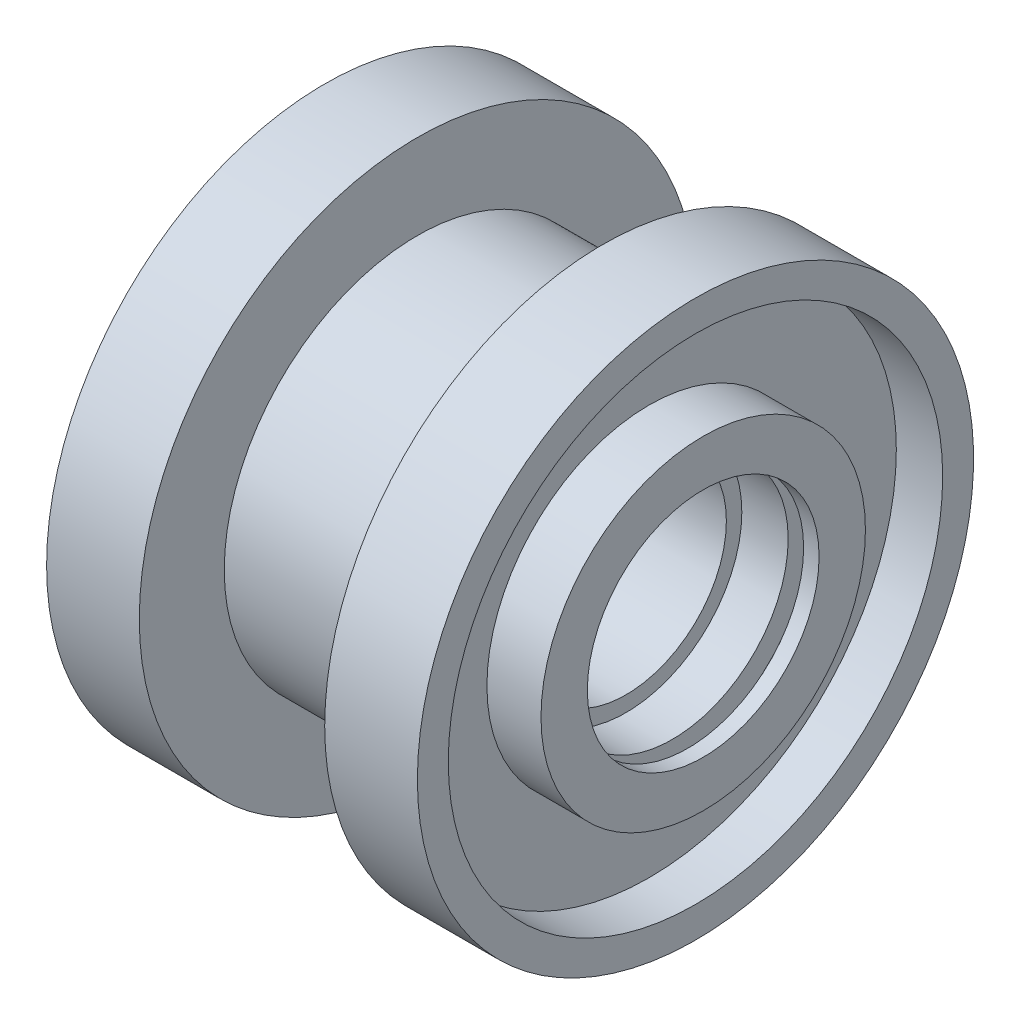
SolidWorks part; units mm, degrees
material "PS HI"
ref_plane "Płaszczyzna przednia" through (0, 0, 0) normal (0, 0, 1) x (1, 0, 0)
ref_plane "Płaszczyzna górna" through (0, 0, 0) normal (0, 1, 0) x (1, 0, 0)
ref_plane "Płaszczyzna prawa" through (0, 0, 0) normal (1, 0, 0) x (0, 0, -1)
sketch "Szkic1" plane through (0, 0, 0) normal (0, 0, 1) x (1, 0, 0)
  line L0 (-12.5, 0) -> (12.5, 0) construction
  line L1 (0, -18) -> (0, 18) construction
  line L2 (-6, 12.5) -> (6, 12.5)
  line L3 (6, 12.5) -> (6, 18)
  line L4 (6, 18) -> (12, 18)
  line L5 (12, 18) -> (12, 16)
  line L6 (12, 16) -> (9, 16)
  line L7 (9, 16) -> (9, 10.5)
  line L10 (-12, 16) -> (-9, 16)
  line L11 (-12, 18) -> (-12, 16)
  line L12 (-6, 18) -> (-12, 18)
  line L13 (-6, 12.5) -> (-6, 18)
  line L15 (12.5, 7.5) -> (12.5, 10.5)
  line L16 (12.5, 10.5) -> (9, 10.5)
  line L18 (-9, 16) -> (-9, 10.5)
  line L20 (-12.5, 7.5) -> (-12.5, 10.5)
  line L21 (-12.5, 10.5) -> (-9, 10.5)
  line L22 (12.5, 7.5) -> (11.5, 7.5)
  line L23 (7.5, 7.5) -> (7.5, 6.5)
  line L24 (7.5, 6.5) -> (-7.5, 6.5)
  line L25 (-7.5, 7.5) -> (-10.5, 7.5)
  line L26 (-7.5, 7.5) -> (-7.5, 6.5)
  line L27 (11.5, 7.5) -> (11.5, 8.9)
  line L28 (11.5, 8.9) -> (10.5, 8.9)
  line L29 (10.5, 8.9) -> (10.5, 7.5)
  line L30 (10.5, 7.5) -> (7.5, 7.5)
  line L31 (-11.5, 7.5) -> (-11.5, 8.9)
  line L32 (-10.5, 8.9) -> (-10.5, 7.5)
  line L33 (-11.5, 8.9) -> (-10.5, 8.9)
  line L34 (-11.5, 7.5) -> (-12.5, 7.5)
  point P1 (12, 17)
  point P7 (0, 0)
  point P14 (0, 7.5)
  point P15 (7.5, 7.5)
  point P21 (0, 12.5)
  point P23 (12.5, 9)
  point P32 (0, 6.5)
  point P40 (0, 0)
  point P41 (0, 0)
  point P42 (0, 0)
  point P43 (0, 0)
  dimension "D2" = 25
  dimension "D3" = 32
  dimension "D4" = 36
  dimension "D5" = 3
  dimension "D6" = 6
  dimension "D7" = 12
  dimension "D8" = 21
  dimension "D9" = 3.5
  dimension "D10" = 25
  dimension "D11" = 5
  dimension "D12" = 13
  dimension "D14" = 1
  dimension "D15" = 3
  dimension "D16" = 15
  dimension "D17" = 17.8
revolve "Obrót1" add sketch "Szkic1" angle 360 about L0
sketch "Szkic2" plane through (-12, 0, 0) normal (-1, 0, 0) x (0, 0, 1)
  line L0 (0, 18) -> (0, 16) construction
  circle A0 centre (0, 17) radius 0.5
  dimension "D1" = 1
extrude "Wytnij-wyciągnięcie1" cut sketch "Szkic2" against normal blind 1
